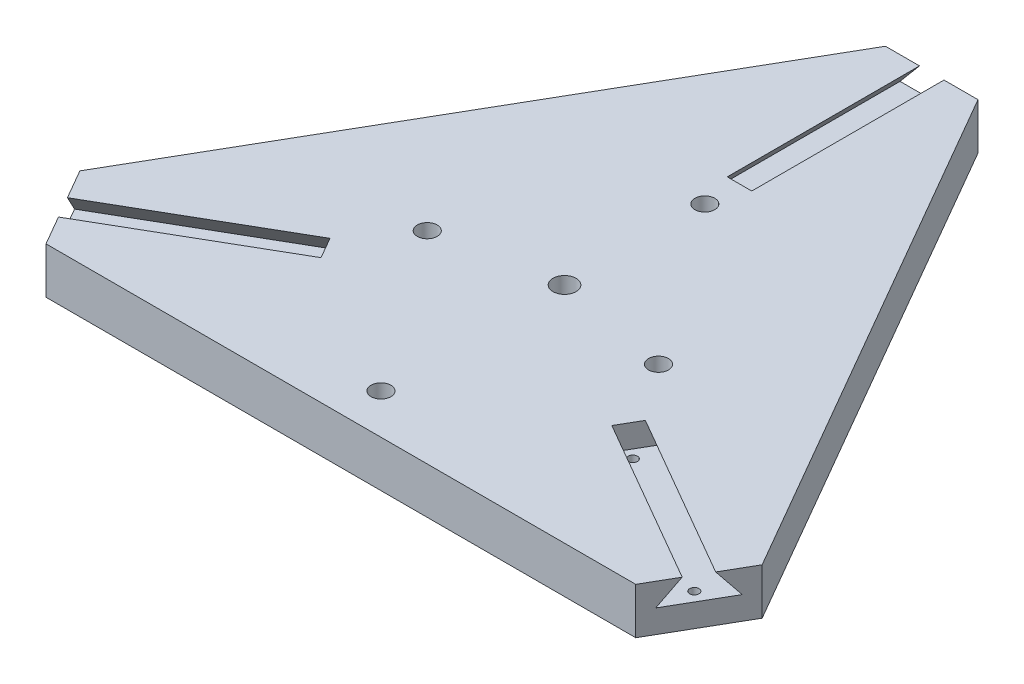
SolidWorks part; units mm, degrees
ref_plane "Plan de face" through (0, 0, 0) normal (0, 0, 1) x (1, 0, 0)
ref_plane "Plan de dessus" through (0, 0, 0) normal (0, 1, 0) x (1, 0, 0)
ref_plane "Plan de droite" through (0, 0, 0) normal (1, 0, 0) x (0, 0, -1)
sketch "Esquisse1" plane through (0, 0, 0) normal (0, 1, 0) x (1, 0, 0)
  line L29 (-10, 79.3725) -> (10, 79.3725)
  line L30 (73.7386, -31.026) -> (63.7386, -48.3465)
  line L31 (-63.7386, -48.3465) -> (-73.7386, -31.026)
  line L32 (-10, 79.3725) -> (-73.7386, -31.026)
  line L33 (-63.7386, -48.3465) -> (63.7386, -48.3465)
  line L34 (73.7386, -31.026) -> (10, 79.3725)
  circle A7 centre (0, 0) radius 2.5
  circle A8 centre (0, 0) radius 79.3725 construction
  point P17 (0, 0)
  dimension "D1" = 20
  dimension "D4" = 20
  dimension "D5" = 80
  dimension "D6" = 80
  dimension "D3" = 80
  dimension "D9" = 5
  dimension "D12" = 79.3725
  dimension "D2" = 20
  dimension "D7" = 60
  dimension "D8" = 60
  dimension "D10" = 80
  dimension "D11" = 80
extrude "Boss.-Extru.1" add sketch "Esquisse1" along normal mid plane 10
sketch "Esquisse2" plane through (0, 5, 0) normal (0, 1, 0) x (1, 0, 0)
  line L0 (-68.7386, -39.6863) -> (0, 0) construction
  line L1 (-73.7386, -31.026) -> (-63.7386, -48.3465) construction
  circle A0 centre (-66.3571, -38.3113) radius 1
  circle A1 centre (-34.9203, -20.1613) radius 1
  dimension "D1" = 2
  dimension "D4" = 2
  dimension "D2" = 2.75
  dimension "D3" = 39.05
extrude "Enlèv. mat.-Extru.1" cut sketch "Esquisse2" against normal through all
pattern_circular "Répétition circulaire1" count 3 over 360 about axis through (0, 5, 0) along (0, -1, 0) of "Enlèv. mat.-Extru.1" reverse direction yes
sketch "Esquisse3" plane through (68.7386, 0, 39.6863) normal (0.866, 0, 0.5) x (0.5, 0, -0.866)
  line L0 (2.65, 5) -> (6.845, 0)
  line L1 (-10, 5) -> (10, 5) construction
  line L3 (-6.845, 0) -> (-2.65, 5)
  line L4 (-2.65, 5) -> (2.65, 5)
  line L6 (-6.845, 0) -> (6.845, 0)
  point P1 (0, 0)
  point P2 (0, 0)
  point P6 (0, 5)
  point P11 (0, 0)
  point P12 (7.039, 0)
  dimension "D1" = 5.3
  dimension "D2" = 13.69
extrude "Enlèv. mat.-Extru.2" cut sketch "Esquisse3" against normal blind 41.553
pattern_circular "Répétition circulaire2" count 3 over 360 about axis through (0, 5, 0) along (0, -1, 0) of "Enlèv. mat.-Extru.2"
sketch "Esquisse4" plane through (0, -5, 0) normal (0, -1, 0) x (1, 0, 0)
  line L0 (0, 0) -> (25, 0) construction
  line L1 (25, 0) -> (25, 4.68) construction
  line L2 (0, 0) -> (-25, 0) construction
  line L3 (-25, 0) -> (-25, 4.68) construction
  circle A3 centre (0, -30.3225) radius 2.15
  circle A4 centre (0, -40.3225) radius 1 construction
  circle A7 centre (0, 39.68) radius 2.15
  circle A8 centre (25, 4.68) radius 2.15
  circle A9 centre (-25, 4.68) radius 2.15
  point P7 (0, 0)
  point P15 (0, 0)
  dimension "D3" = 25
  dimension "D4" = 4.68
  dimension "D7" = 4.3
  dimension "D8" = 39.68
  dimension "D1" = 10
  dimension "D2" = 4.3
  dimension "D5" = 25
  dimension "D9" = 4.3
  dimension "D10" = 4.3
  dimension "D6" = 4.68
extrude "Enlèv. mat.-Extru.3" cut sketch "Esquisse4" against normal through all
